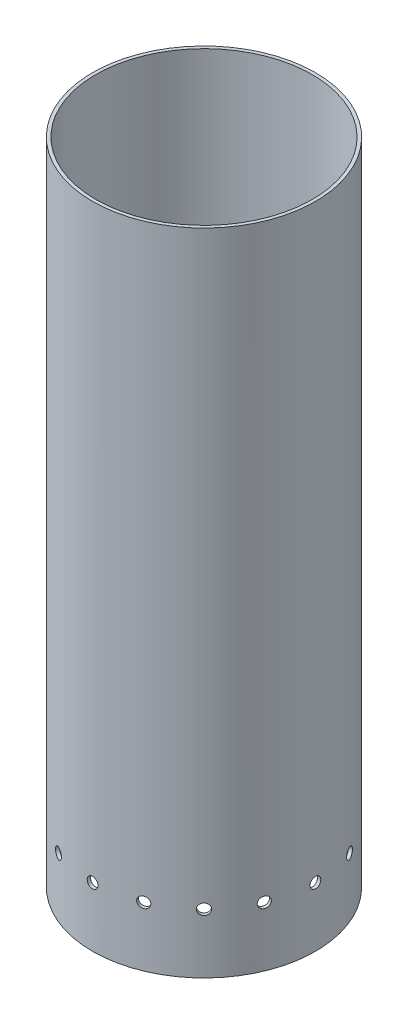
SolidWorks part; units mm, degrees
ref_plane "Front Plane" through (0, 0, 0) normal (0, 0, 1) x (1, 0, 0)
ref_plane "Top Plane" through (0, 0, 0) normal (0, 1, 0) x (1, 0, 0)
ref_plane "Right Plane" through (0, 0, 0) normal (1, 0, 0) x (0, 0, -1)
sketch "Sketch1" plane through (0, 0, 0) normal (0, 1, 0) x (1, 0, 0)
  circle A0 centre (0, 0) radius 63.5
  circle A1 centre (0, 0) radius 65.405
  dimension "D1" = 127
  dimension "D2" = 130.81
extrude "Boss-Extrude1" add sketch "Sketch1" against normal blind 381
ref_plane "Plane1" through (0, 0, 65.405) normal (0, 0, 1) x (1, 0, 0)
ref_axis "Axis1" through (0, -381, 0) along (0, 1, 0)
sketch "Sketch4" plane through (0, 0, 65.405) normal (0, 0, 1) x (1, 0, 0)
  line L2 (-65.405, -381) -> (65.405, -381) construction
  circle A0 centre (0, -346.075) radius 3.175
  point P0 (0, -346.075)
  dimension "D2" = 6.35
  dimension "D1" = 34.925
extrude "Cut-Extrude3" cut sketch "Sketch4" against normal up to next
pattern_circular "CirPattern2" count 16 over 360 about axis through (0, -381, 0) along (0, 1, 0) of "Cut-Extrude3"
